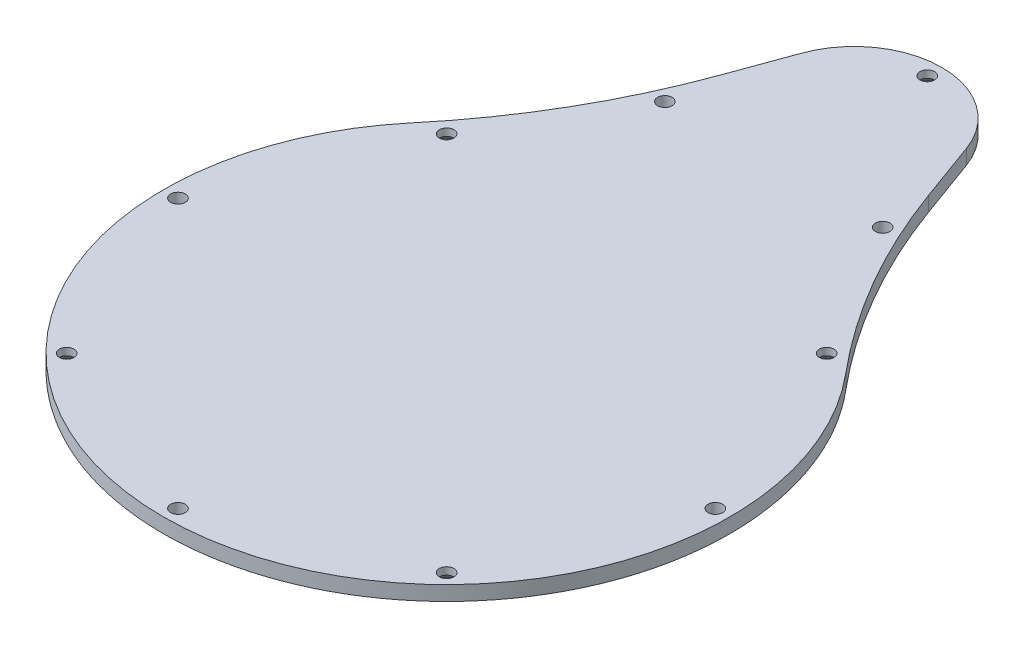
SolidWorks part; units mm, degrees
ref_plane "Front Plane" through (0, 0, 0) normal (0, 0, 1) x (1, 0, 0)
ref_plane "Top Plane" through (0, 0, 0) normal (0, 1, 0) x (1, 0, 0)
ref_plane "Right Plane" through (0, 0, 0) normal (1, 0, 0) x (0, 0, -1)
sketch "Sketch1" plane through (0, -109.25, 0) normal (0, -1, 0) x (1, 0, 0)
  line L2 (-45.3132, -163.9748) -> (-35.8023, -190.106)
  line L3 (35.8023, -190.106) -> (45.3132, -163.9748)
  line L4 (-45.3132, -163.9748) -> (-35.8023, -190.106)
  line L5 (35.8023, -190.106) -> (45.3132, -163.9748)
  line L6 (23.8682, -185.7623) -> (33.3792, -159.6312)
  line L7 (-33.3792, -159.6312) -> (-23.8682, -185.7623)
  line L8 (23.8682, -185.7623) -> (33.3792, -159.6312)
  line L9 (-33.3792, -159.6312) -> (-23.8682, -185.7623)
  circle A1 centre (-82.5547, -82.5547) radius 3.175
  circle A2 centre (-82.5547, -82.5547) radius 3.175
  circle A3 centre (-47.3293, -142.15) radius 3.175
  arc A4 (-35.8023, -190.106) -> (35.8023, -190.106) centre (0, -177.075) ccw
  arc A5 (94.3001, -79.1272) -> (45.3132, -163.9748) centre (310.4042, -260.46) ccw
  arc A6 (94.3001, -79.1272) -> (-94.3001, -79.1272) centre (0, 0) ccw
  arc A7 (-45.3132, -163.9748) -> (-94.3001, -79.1272) centre (-310.4042, -260.46) ccw
  arc A8 (-35.8023, -190.106) -> (35.8023, -190.106) centre (0, -177.075) ccw
  arc A9 (94.3001, -79.1272) -> (45.3132, -163.9748) centre (310.4042, -260.46) ccw
  arc A10 (94.3001, -79.1272) -> (-94.3001, -79.1272) centre (0, 0) ccw
  arc A11 (-45.3132, -163.9748) -> (-94.3001, -79.1272) centre (-310.4042, -260.46) ccw
  circle A12 centre (-47.3293, -142.15) radius 3.175
  circle A13 centre (0, -208.825) radius 3.175
  circle A14 centre (0, -208.825) radius 3.175
  circle A15 centre (47.3293, -142.15) radius 3.175
  circle A16 centre (47.3293, -142.15) radius 3.175
  circle A17 centre (82.5547, -82.5547) radius 3.175
  circle A18 centre (82.5547, -82.5547) radius 3.175
  circle A19 centre (116.75, 0) radius 3.175
  circle A20 centre (116.75, 0) radius 3.175
  circle A21 centre (82.5547, 82.5547) radius 3.175
  circle A22 centre (82.5547, 82.5547) radius 3.175
  circle A23 centre (0, 116.75) radius 3.175
  circle A24 centre (0, 116.75) radius 3.175
  circle A25 centre (-82.5547, 82.5547) radius 3.175
  circle A26 centre (-82.5547, 82.5547) radius 3.175
  circle A27 centre (-116.75, 0) radius 3.175
  circle A28 centre (-116.75, 0) radius 3.175
  arc A32 (-33.3792, -159.6312) -> (-84.5713, -70.9638) centre (-310.4042, -260.46) ccw
  arc A33 (84.5713, -70.9638) -> (-84.5713, -70.9638) centre (0, 0) ccw
  arc A34 (84.5713, -70.9638) -> (33.3792, -159.6312) centre (310.4042, -260.46) ccw
  arc A35 (-23.8682, -185.7623) -> (23.8682, -185.7623) centre (0, -177.075) ccw
  arc A36 (-33.3792, -159.6312) -> (-84.5713, -70.9638) centre (-310.4042, -260.46) ccw
  arc A37 (84.5713, -70.9638) -> (-84.5713, -70.9638) centre (0, 0) ccw
  arc A38 (84.5713, -70.9638) -> (33.3792, -159.6312) centre (310.4042, -260.46) ccw
  arc A39 (-23.8682, -185.7623) -> (23.8682, -185.7623) centre (0, -177.075) ccw
  circle M23 centre (47.3293, -142.15) radius 3.175
  circle M24 centre (116.75, 0) radius 3.175
  circle M25 centre (0, 116.75) radius 3.175
  circle M26 centre (-116.75, 0) radius 3.175
  circle M27 centre (-47.3293, -142.15) radius 3.175
  arc M28 (94.3001, -79.1272) -> (-94.3001, -79.1272) centre (0, 0) ccw
  arc M29 (-94.3001, -79.1272) -> (-45.3132, -163.9748) centre (-310.4042, -260.46) cw
  line M30 (-45.3132, -163.9748) -> (-35.8023, -190.106)
  arc M31 (-35.8023, -190.106) -> (35.8023, -190.106) centre (0, -177.075) ccw
  line M32 (35.8023, -190.106) -> (45.3132, -163.9748)
  arc M33 (45.3132, -163.9748) -> (94.3001, -79.1272) centre (310.4042, -260.46) cw
  circle M34 centre (-82.5547, -82.5547) radius 3.175
  circle M35 centre (-82.5547, 82.5547) radius 3.175
  circle M36 centre (82.5547, 82.5547) radius 3.175
  circle M37 centre (82.5547, -82.5547) radius 3.175
  circle M38 centre (0, -208.825) radius 3.175
  line M39 (33.3792, -159.6312) -> (23.8682, -185.7623)
  arc M40 (23.8682, -185.7623) -> (-23.8682, -185.7623) centre (0, -177.075) cw
  line M41 (-23.8682, -185.7623) -> (-33.3792, -159.6312)
  arc M42 (-33.3792, -159.6312) -> (-84.5713, -70.9638) centre (-310.4042, -260.46) ccw
  arc M43 (-84.5713, -70.9638) -> (84.5713, -70.9638) centre (0, 0) cw
  arc M44 (84.5713, -70.9638) -> (33.3792, -159.6312) centre (310.4042, -260.46) ccw
  dimension "D1" = 0
  dimension "D2" = 0
  dimension "D3" = 0
  dimension "D4" = 0
  dimension "D5" = 0
  dimension "D6" = 0
  dimension "D7" = 0
  dimension "D8" = 0
  dimension "D9" = 0
  dimension "D10" = 0
  dimension "D11" = 0
  dimension "D12" = 0
extrude "Boss-Extrude1" add sketch "Sketch1" along normal blind 6.35 contours M33 M28 M29 M30 M31 M32 M24 M26 M35 M37 M44 M39 M40 M41 M42 M43 M38 M36 M34 M27 M25 M23 | A36 A37 A38 L8 A39 L9 region at (-62.4718, -109.25, -117.3162)
chamfer "Chamfer1" distance 3.175 5 edges at (82.5547, -115.6, -85.7297) (82.5547, -115.6, 79.3797) (-82.5547, -115.6, 79.3797) (-82.5547, -115.6, -85.7297) (0, -115.6, -212)
